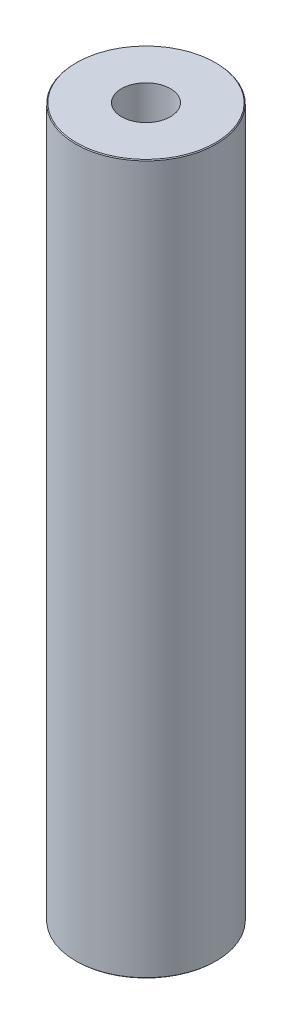
SolidWorks part; units mm, degrees
ref_plane "Front Plane" through (0, 0, 0) normal (0, 0, 1) x (1, 0, 0)
ref_plane "Top Plane" through (0, 0, 0) normal (0, 1, 0) x (1, 0, 0)
ref_plane "Right Plane" through (0, 0, 0) normal (1, 0, 0) x (0, 0, -1)
sketch "Sketch1" plane through (0, 0, 0) normal (0, 1, 0) x (1, 0, 0)
  circle A0 centre (0, 0) radius 45
  dimension "SHAFT_OD" = 90
extrude "Boss-Extrude1" add sketch "Sketch1" along normal blind 454.2266
sketch "Sketch2" plane through (0, 0, 0) normal (0, 1, 0) x (1, 0, 0)
  circle A0 centre (0, 0) radius 15.6469
  dimension "BORE_D" = 31.2939
extrude "Cut-Extrude1" cut sketch "Sketch2" along normal through all
chamfer "Chamfer1" distance 0.5078 angle 45 2 edges at (0, 454.2266, 45) (0, 0, 45)
